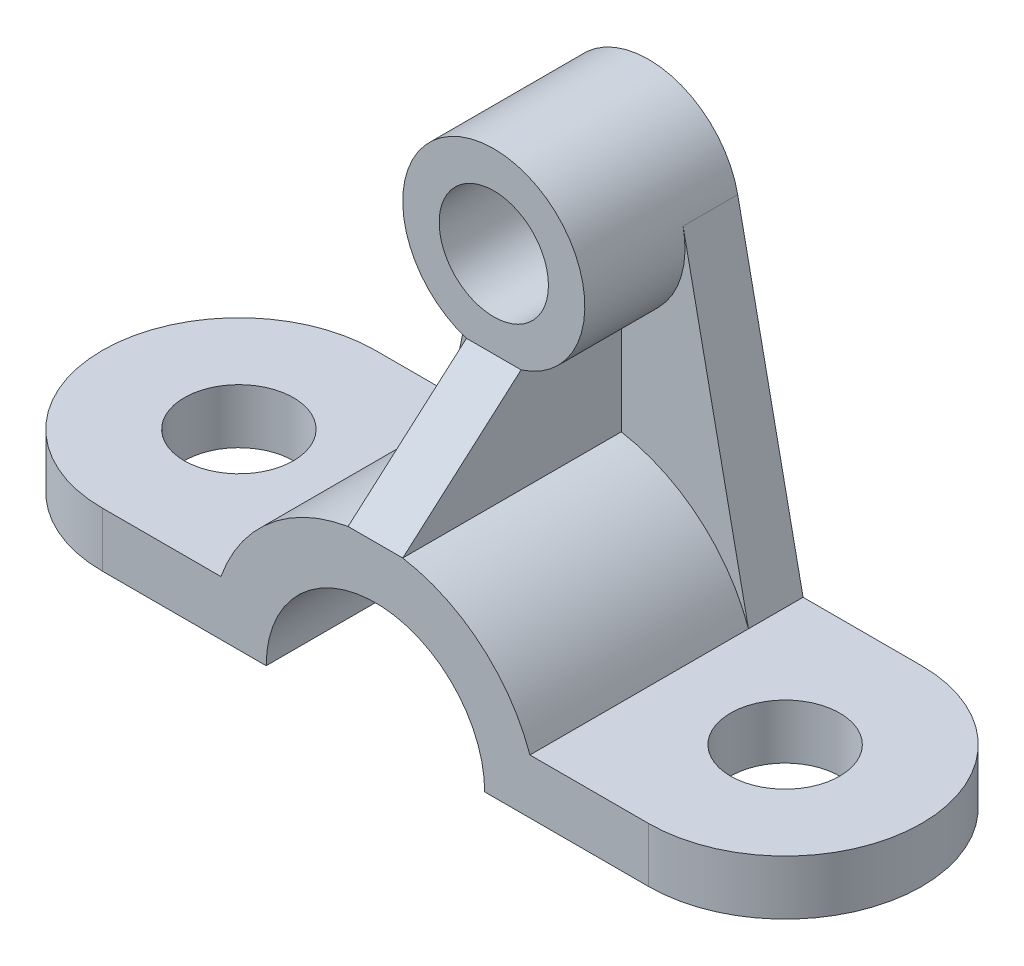
SolidWorks part; units mm, degrees
ref_plane "Ön Düzlem" through (0, 0, 0) normal (0, 0, 1) x (1, 0, 0)
ref_plane "Üst Düzlem" through (0, 0, 0) normal (0, 1, 0) x (1, 0, 0)
ref_plane "Sağ Düzlem" through (0, 0, 0) normal (1, 0, 0) x (0, 0, -1)
sketch "Çizim1" plane through (0, 0, 0) normal (0, 0, 1) x (1, 0, 0)
  line L0 (-102.9704, 18.3988) -> (-168.9704, 18.3988)
  line L1 (-168.9704, 18.3988) -> (-168.9704, 30.3988)
  line L2 (-168.9704, 30.3988) -> (-112.9115, 30.3988)
  line L3 (-54.9704, 18.3988) -> (11.0296, 18.3988)
  line L4 (11.0296, 18.3988) -> (11.0296, 30.3988)
  line L5 (11.0296, 30.3988) -> (-45.0292, 30.3988)
  arc A1 (-54.9704, 18.3988) -> (-102.9704, 18.3988) centre (-78.9704, 18.3988) ccw
  arc A2 (-45.0292, 30.3988) -> (-112.9115, 30.3988) centre (-78.9704, 18.3988) ccw
  point P1 (0, 0)
  point P2 (0, 0)
  point P10 (0, 0)
  point P12 (0, 0)
  dimension "D1" = 12
  dimension "D2" = 48
  dimension "D6" = 12
  dimension "D3" = 12
  dimension "D4" = 180
  dimension "D5" = 66
extrude "Yükseklik-Ekstrüzyon1" add sketch "Çizim1" along normal blind 60
fillet "Radyus1" 2 edges at (-168.9704, 24.3988, 0) (-168.9704, 24.3988, 60) type full round first side face at (-78.9704, 30.3988, 0) second side face at (-78.9704, 30.3988, 60) middle face at (-168.9704, 24.3988, 30)
fillet "Radyus2" 2 edges at (11.0296, 24.3988, 0) (11.0296, 24.3988, 60) type full round first side face at (-71.4704, 30.3988, 0) second side face at (-71.4704, 30.3988, 60) middle face at (11.0296, 24.3988, 30)
sketch "Çizim3" plane through (0, 30.3988, 0) normal (0, 1, 0) x (1, 0, 0)
  circle A0 centre (-138.9704, -30) radius 12
  circle A1 centre (-18.9704, -30) radius 12
  dimension "D1" = 24
  dimension "D2" = 24
extrude "Kes-Ekstrüzyon1" cut sketch "Çizim3" against normal through all contours A1 | A0
ref_plane "Düzlem1" through (0, 0, 0) normal (0, 0, -1) x (-1, 0, 0)
sketch "Çizim4" plane through (0, 0, 0) normal (0, 0, -1) x (-1, 0, 0)
  line L0 (59.3847, 99.8219) -> (45.0292, 30.3988)
  line L1 (98.556, 99.8219) -> (112.9115, 30.3988)
  line L2 (45.0292, 30.3988) -> (45.0292, 18.3988)
  line L3 (54.9704, 18.3988) -> (18.9704, 18.3988) construction
  line L4 (45.0292, 18.3988) -> (112.9115, 18.3988)
  line L5 (138.9704, 18.3988) -> (102.9704, 18.3988) construction
  line L6 (112.9115, 18.3988) -> (112.9115, 30.3988)
  arc A0 (98.556, 99.8219) -> (59.3847, 99.8219) centre (78.9704, 95.7719) ccw
  point P4 (78.9704, 18.3988)
  dimension "D1" = 40
extrude "Yükseklik-Ekstrüzyon2" add sketch "Çizim4" against normal blind 12
sketch "Çizim5" plane through (0, 0, 12) normal (0, 0, 1) x (1, 0, 0)
  circle A0 centre (-78.9704, 95.7719) radius 20
  circle A1 centre (-78.9704, 95.7719) radius 12
  dimension "D1" = 24
extrude "Yükseklik-Ekstrüzyon3" add sketch "Çizim5" along normal blind 22
sketch "Çizim7" plane through (0, 0, 12) normal (0, 0, 1) x (1, 0, 0)
  line L0 (-54.9704, 18.3988) -> (-102.9704, 18.3988) construction
  line L1 (-84.9704, 79.224) -> (-72.9704, 79.224)
  line L2 (-84.9704, 79.224) -> (-84.9704, 49.5122)
  line L3 (-84.9704, 49.5122) -> (-72.9704, 49.5122)
  line L4 (-72.9704, 79.224) -> (-72.9704, 49.5122)
  point P6 (-78.9704, 18.3988)
  dimension "D1" = 12
  dimension "D2" = 6
  dimension "D3" = 12
extrude "Yükseklik-Ekstrüzyon6" add sketch "Çizim7" along normal blind 48
sketch "Çizim8" plane through (-84.9704, 0, 0) normal (-1, 0, 0) x (0, 0, 1)
  line L0 (34, 76.6931) -> (34, 79.224)
  line L1 (34, 79.224) -> (60, 79.224)
  line L2 (60, 79.224) -> (60, 53.8953)
  line L3 (60, 53.8953) -> (34, 76.6931)
extrude "Kes-Ekstrüzyon2" cut sketch "Çizim8" against normal through all
sketch "Çizim9" plane through (0, 0, 12) normal (0, 0, 1) x (1, 0, 0)
  line L0 (-54.9704, 18.3988) -> (-102.9704, 18.3988) construction
  circle A0 centre (-78.9704, 18.3988) radius 24
extrude "Kes-Ekstrüzyon3" cut sketch "Çizim9" against normal through all
